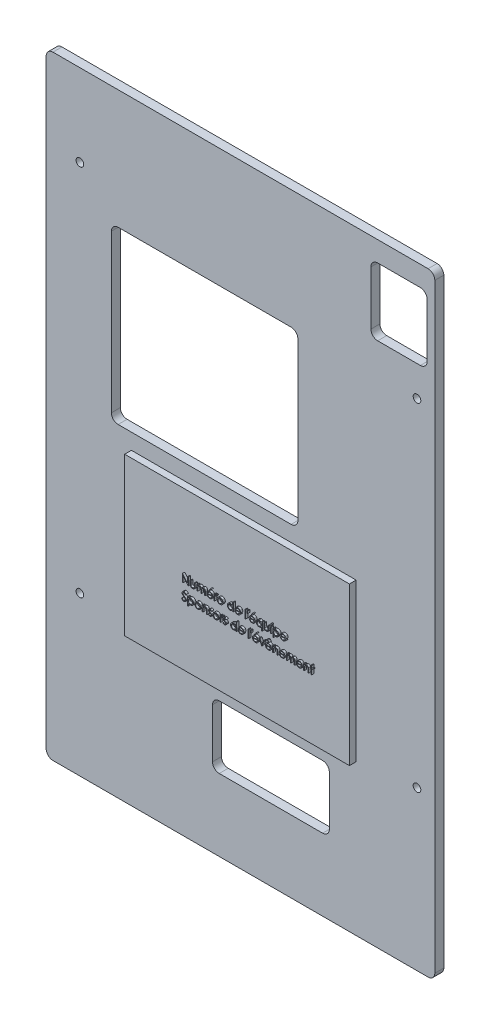
SolidWorks part; units mm, degrees
material "Verre"
ref_plane "Plan de face" through (0, 0, 0) normal (0, 0, 1) x (1, 0, 0)
ref_plane "Plan de dessus" through (0, 0, 0) normal (0, 1, 0) x (1, 0, 0)
ref_plane "Plan de droite" through (0, 0, 0) normal (1, 0, 0) x (0, 0, -1)
sketch "Esquisse1" plane through (0, 0, 0) normal (0, 0, 1) x (1, 0, 0)
  line L1 (0, 0) -> (172.93, 0)
  line L2 (0, 0) -> (0, 273)
  line L3 (0, 273) -> (172.93, 273)
  line L4 (172.93, 0) -> (172.93, 273)
  line L5 (74, 60) -> (126, 60)
  line L6 (74, 60) -> (74, 32)
  line L7 (74, 32) -> (126, 32)
  line L8 (126, 60) -> (126, 32)
  line L9 (29, 220) -> (112, 220)
  line L10 (29, 220) -> (29, 144)
  line L11 (29, 144) -> (112, 144)
  line L12 (112, 220) -> (112, 144)
  line L13 (169.5, 264) -> (144.5, 264)
  line L14 (169.5, 264) -> (169.5, 234)
  line L15 (169.5, 234) -> (144.5, 234)
  line L16 (144.5, 264) -> (144.5, 234)
  line L17 (169.5, 264) -> (144.5, 234) construction
  line L18 (169.5, 234) -> (144.5, 264) construction
  circle A0 centre (15, 236.5) radius 1.5
  circle A1 centre (165, 220.5) radius 1.5
  circle A2 centre (15, 70.5) radius 1.5
  circle A3 centre (165, 70.5) radius 1.5
  point P21 (157, 249)
  dimension "D5" = 3
  dimension "D8" = 3
  dimension "D11" = 3
  dimension "D22" = 3
  dimension "D25" = 25
  dimension "D1" = 172.93
  dimension "D2" = 273
  dimension "D3" = 36.5
  dimension "D4" = 15
  dimension "D6" = 7.93
  dimension "D7" = 52.5
  dimension "D9" = 70.5
  dimension "D10" = 15
  dimension "D12" = 74
  dimension "D13" = 52
  dimension "D14" = 28
  dimension "D15" = 32
  dimension "D16" = 29
  dimension "D17" = 83
  dimension "D18" = 144
  dimension "D19" = 76
  dimension "D20" = 7.93
  dimension "D21" = 70.5
  dimension "D23" = 15.93
  dimension "D24" = 24
  dimension "D26" = 30
extrude "Boss.-Extru.1" add sketch "Esquisse1" along normal blind 4
hole_wizard "Dégagement M31" positions "Esquisse2" profile "Esquisse3" hole size "M3" standard "ISO" end condition through all
sketch "Esquisse2" plane through (0, 0, 4) normal (0, 0, 1) x (1, 0, 0)
  point P0 (15, 236.5)
  point P3 (15, 70.5)
  point P6 (165, 220.5)
  point P9 (165, 70.5)
sketch "Esquisse3" plane through (15, 236.5, 4) normal (1, 0, 0) x (0, -1, 0)
  line L0 (0, 0) -> (0, 4)
  line L1 (0, 4) -> (1.7, 4)
  line L2 (1.7, 4) -> (1.7, 0)
  line L5 (1.7, 0) -> (0, 0)
  line L11 (0, -6.35) -> (0, 107.95) construction
  dimension "Diamètre du perçage jusqu'au prochain" = 3.4
  dimension "Profondeur du perçage jusqu'au prochain" = 4
fillet "Congé1" radius 3 16 edges at (0, 0, 2) (172.93, 0, 2) (126, 32, 2) (74, 32, 2) (126, 60, 2) (74, 60, 2) (112, 144, 2) (29, 144, 2) (112, 220, 2) (29, 220, 2) (172.93, 273, 2) (0, 273, 2) (169.5, 234, 2) (169.5, 264, 2) (144.5, 264, 2) (144.5, 234, 2)
sketch "Esquisse5" plane through (0, 0, 4) normal (0, 0, 1) x (1, 0, 0)
  line L0 (32, 144) -> (109, 144) construction
  line L1 (37.93, 137) -> (137.93, 137)
  line L2 (37.93, 137) -> (37.93, 67)
  line L3 (37.93, 67) -> (137.93, 67)
  line L4 (137.93, 137) -> (137.93, 67)
  line L5 (172.93, 3) -> (172.93, 270) construction
  line L6 (37.93, 102) -> (137.93, 102) construction
  dimension "D1" = 100
  dimension "D2" = 70
  dimension "D3" = 7
  dimension "D4" = 35
extrude "Boss.-Extru.3" add sketch "Esquisse5" along normal blind 3 contours L2 L3 L4 L1
sketch "Esquisse6" plane through (0, 0, 7) normal (0, 0, 1) x (1, 0, 0)
  text T0 "Numéro de l'équipe\r\nSponsors de l'évènement"
extrude "Boss.-Extru.4" add sketch "Esquisse6" along normal blind 1
